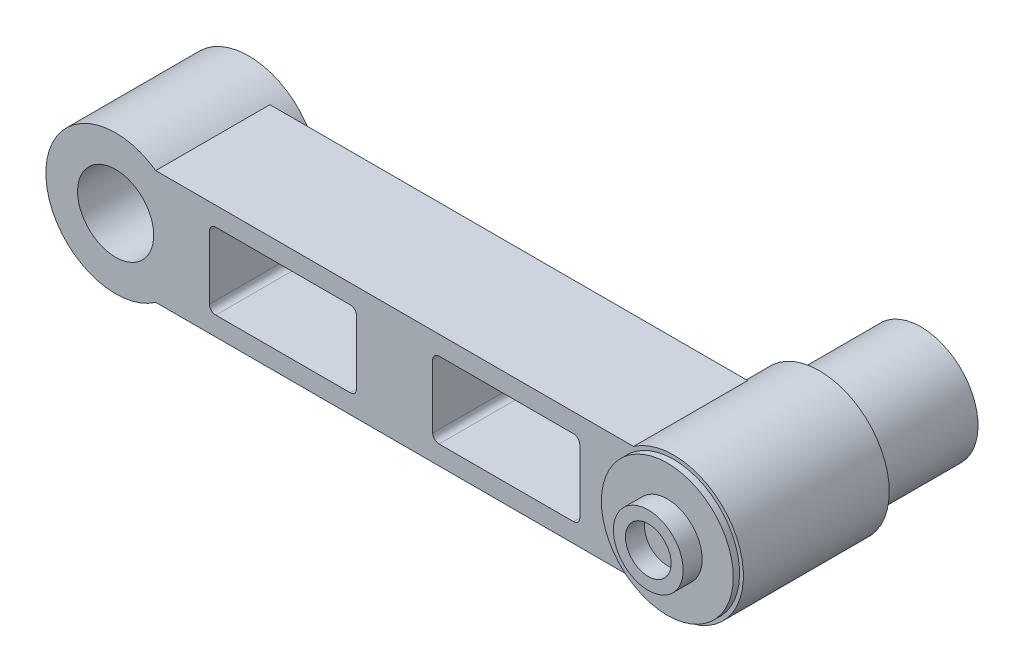
SolidWorks part; units mm, degrees
material "Cast Stainless Steel"
ref_plane "Front Plane" through (0, 0, 0) normal (0, 0, 1) x (1, 0, 0)
ref_plane "Top Plane" through (0, 0, 0) normal (0, 1, 0) x (1, 0, 0)
ref_plane "Right Plane" through (0, 0, 0) normal (1, 0, 0) x (0, 0, -1)
other "Center of Mass"
sketch "Sketch11" plane through (0, 0, 0) normal (0, 0, 1) x (1, 0, 0)
  line L0 (0, 440) -> (0, 0) construction
  line L1 (45, 31.6228) -> (45, 408.3772)
  line L4 (-45, 31.6228) -> (-45, 408.3772)
  circle A0 centre (0, 0) radius 55
  circle A1 centre (0, 440) radius 55
  dimension "D1" = 110
  dimension "D2" = 110
  dimension "D3" = 45
  dimension "D4" = 45
  dimension "D5" = 440
extrude "Boss-Extrude5" add sketch "Sketch11" along normal blind 90 contours A1 L4 A0 L1 | L0 A1 L4 A0 | A1 | A0 region at (22.9783, 220, 0) region at (-22.9783, 220, 0) region at (-24.6378, 392.5734, 0) region at (24.6378, 47.4266, 0)
extrude "Boss-Extrude6" add sketch "Sketch11<3>" along normal blind 115 contours A1 region at (0, 440, 0)
sketch "Sketch11<3>" plane through (0, 0, 0) normal (0, 0, 1) x (1, 0, 0) same geometry as "Sketch11"
extrude "Boss-Extrude7" add sketch "Sketch11<4>" along normal blind 105 contours A0 region at (0, 0, 0)
sketch "Sketch11<4>" plane through (0, 0, 0) normal (0, 0, 1) x (1, 0, 0) same geometry as "Sketch11"
sketch "Sketch13" plane through (0, 0, 90) normal (0, 0, 1) x (1, 0, 0)
  line L2 (7.6389, 82) -> (7.6389, 54.4669)
  line L3 (7.6389, 54.4669) -> (-7.6389, 54.4669)
  line L4 (-7.6389, 82) -> (-7.6389, 54.4669)
  arc A1 (7.6389, 82) -> (-7.6389, 82) centre (0, 82) ccw
  arc A2 (45, 31.6228) -> (-45, 31.6228) centre (0, 0) ccw construction
extrude "Boss-Extrude8" add sketch "Sketch13" along normal blind 15
sketch "Sketch17" plane through (0, 0, 115) normal (0, 0, 1) x (1, 0, 0)
  circle A0 centre (0, 440) radius 45
extrude "Boss-Extrude9" add sketch "Sketch17" along normal blind 80
sketch "Sketch18" plane through (0, 0, 0) normal (0, 0, -1) x (-1, 0, 0)
  circle A0 centre (0, 440) radius 52
extrude "Boss-Extrude10" add sketch "Sketch18" along normal blind 5
sketch "Sketch19" plane through (0, 0, -5) normal (0, 0, -1) x (-1, 0, 0)
  circle A0 centre (0, 440) radius 37.5
  circle A1 centre (0, 440) radius 27.5
  circle A2 centre (0, 440) radius 18
extrude "Boss-Extrude12" add sketch "Sketch19" along normal blind 15 contours A2 | A1
ref_plane "Plane1" through (0, 0, 167.63) normal (0, 0, -1) x (-1, 0, 0)
move or copy body "Body-Move/Copy2" bodies to move or copy 113 copy no rotation origin (0, 0, 0) rotation axis (0, 1, 0) rotation angle 180
sketch "Sketch28" plane through (0, 0, -105) normal (0, 0, -1) x (-1, 0, 0)
  circle A0 centre (0, 0) radius 52
  dimension "D1" = 104
extrude "Cut-Extrude2" cut sketch "Sketch28" against normal blind 60
ref_plane "Plane2" through (0, 0, 10) normal (0, 0, 1) x (1, 0, 0)
sketch "Sketch29" plane through (0, 0, 0) normal (0, 0, 1) x (1, 0, 0)
  line L0 (-30, 250) -> (-30, 190) construction
  line L1 (-25, 190) -> (25, 190)
  line L2 (-30, 185) -> (-30, 79)
  line L3 (-25, 74) -> (25, 74)
  line L4 (30, 185) -> (30, 79)
  line L5 (-25, 366) -> (25, 366)
  line L6 (45, 31.6228) -> (45, 408.3772)
  line L7 (-45, 408.3772) -> (-45, 31.6228)
  line L8 (45, 31.6228) -> (45, 408.3772)
  line L9 (-45, 408.3772) -> (-45, 31.6228)
  line L10 (-30, 361) -> (-30, 255)
  line L11 (-25, 250) -> (25, 250)
  line L12 (30, 361) -> (30, 255)
  line L13 (-30, 220) -> (103.3616, 220) construction
  line L14 (0, 440) -> (0, 0) construction
  arc A0 (25, 250) -> (30, 255) centre (25, 255) ccw
  arc A1 (-25, 250) -> (-30, 255) centre (-25, 255) cw
  arc A2 (-45, 31.6228) -> (45, 31.6228) centre (0, 0) ccw
  arc A3 (45, 408.3772) -> (-45, 408.3772) centre (0, 440) ccw
  arc A4 (-45, 31.6228) -> (45, 31.6228) centre (0, 0) ccw
  arc A5 (45, 408.3772) -> (-45, 408.3772) centre (0, 440) ccw
  arc A6 (30, 361) -> (25, 366) centre (25, 361) ccw
  arc A7 (-30, 361) -> (-25, 366) centre (-25, 361) cw
  arc A8 (30, 79) -> (25, 74) centre (25, 79) cw
  arc A9 (-30, 79) -> (-25, 74) centre (-25, 79) ccw
  arc A10 (30, 185) -> (25, 190) centre (25, 185) ccw
  arc A11 (-30, 185) -> (-25, 190) centre (-25, 185) cw
  point P26 (-30, 366)
  point P29 (30, 74)
  point P32 (-30, 74)
  dimension "D5" = 5
  dimension "D6" = 5
  dimension "D2" = 116
  dimension "D3" = 60
  dimension "D4" = 60
  dimension "D1" = 0
extrude "Cut-Extrude3" cut sketch "Sketch29" against normal offset from surface (80 mm away) 10 contours A7 L10 A1 L11 A0 L12 A6 L5 | A11 L2 A9 L3 A8 L4 A10 L1 region at (0, 132, 0) region at (0, 308, 0) up to face at (0, 143.1191, -90)
sketch "Sketch31" plane through (0, 0, 0) normal (0, 0, 1) x (1, 0, 0)
  line L2 (45, 31.6228) -> (45, 408.3772)
  line L3 (-45, 408.3772) -> (-45, 31.6228)
  line L4 (45, 31.6228) -> (45, 408.3772)
  line L5 (-45, 408.3772) -> (-45, 31.6228)
  circle A0 centre (0, 0) radius 30
  arc A2 (-45, 31.6228) -> (45, 31.6228) centre (0, 0) ccw
  arc A3 (45, 408.3772) -> (-45, 408.3772) centre (0, 440) ccw
  arc A4 (-45, 31.6228) -> (45, 31.6228) centre (0, 0) ccw
  arc A5 (45, 408.3772) -> (-45, 408.3772) centre (0, 440) ccw
  dimension "D2" = 60
  dimension "D1" = 0
extrude "Cut-Extrude6" cut sketch "Sketch31" against normal through all contours A0 region at (0, 0, 0)
move or copy body "Body-Move/Copy3" bodies to move or copy 124 copy no rotation origin (0, 0, -87.5) rotation axis (0, 1, 0) rotation angle 180
move or copy body "Body-Move/Copy4" bodies to move or copy 125 copy no rotation origin (0, 225, 0) rotation axis (0, 0, -1) rotation angle 90
move or copy body "Body-Move/Copy6" bodies to move or copy 126 copy no rotation origin (225, 0, -17.5) rotation axis (0, 1, 0) rotation angle 180
sketch "Sketch33" plane through (0, 0, 35) normal (0, 0, -1) x (-1, 0, 0)
  line L2 (-620.5331, 217.3611) -> (-593, 217.3611)
  line L3 (-593, 232.6389) -> (-620.5331, 232.6389)
  line L4 (-620.5331, 217.3611) -> (-593, 217.3611)
  line L5 (-593, 232.6389) -> (-620.5331, 232.6389)
  arc A2 (-620.5331, 232.6389) -> (-620.5331, 217.3611) centre (-675, 225) ccw
  arc A3 (-593, 217.3611) -> (-593, 232.6389) centre (-593, 225) ccw
  arc A4 (-620.5331, 232.6389) -> (-620.5331, 217.3611) centre (-675, 225) ccw
  arc A5 (-593, 217.3611) -> (-593, 232.6389) centre (-593, 225) ccw
  point P5 (-675, 225)
  dimension "D1" = 0
move or copy body "Body-Move/Copy7" bodies to move or copy 128 copy no translate (-675, -225, -35)
move or copy body "Body-Move/Copy8" bodies to move or copy 129 copy no rotation origin (-225, 0, 0) rotation axis (0, 0, -1) rotation angle 90
move or copy body "Body-Move/Copy9" bodies to move or copy 130 copy no rotation origin (-225, 0, 0) rotation axis (0, 0, -1) rotation angle 90
sketch "Sketch34" plane through (0, 0, 0) normal (0, 0, -1) x (-1, 0, 0)
  line L2 (395.5331, 7.6389) -> (368, 7.6389)
  line L3 (368, -7.6389) -> (395.5331, -7.6389)
  line L4 (395.5331, 7.6389) -> (368, 7.6389)
  line L5 (368, -7.6389) -> (395.5331, -7.6389)
  arc A2 (395.5331, -7.6389) -> (395.5331, 7.6389) centre (450, 0) ccw
  arc A3 (368, 7.6389) -> (368, -7.6389) centre (368, 0) ccw
  arc A4 (395.5331, -7.6389) -> (395.5331, 7.6389) centre (450, 0) ccw
  arc A5 (368, 7.6389) -> (368, -7.6389) centre (368, 0) ccw
  point P0 (208.8383, -418.5805)
  point P5 (450, 0)
  dimension "D1" = 0
move or copy body "Body-Move/Copy10" bodies to move or copy 131 copy no translate (450, 0, 0)
ref_axis "Axis2" through (0, 0, 0) along (0, 0, 1)
ref_plane "Plane10" through (0, 0, -62.63) normal (0, 0, -1) x (-1, 0, 0)
ref_point "Point3"
move or copy body "Body-Move/Copy14" bodies to move or copy 132 copy no translate (0, 0, 62.63)
sketch "Sketch36" plane through (0, 0, -27.37) normal (0, 0, -1) x (-1, 0, 0)
  circle A0 centre (-440, 0) radius 24.5
  dimension "D1" = 49
extrude "Cut-Extrude7" cut sketch "Sketch36" against normal blind 60
